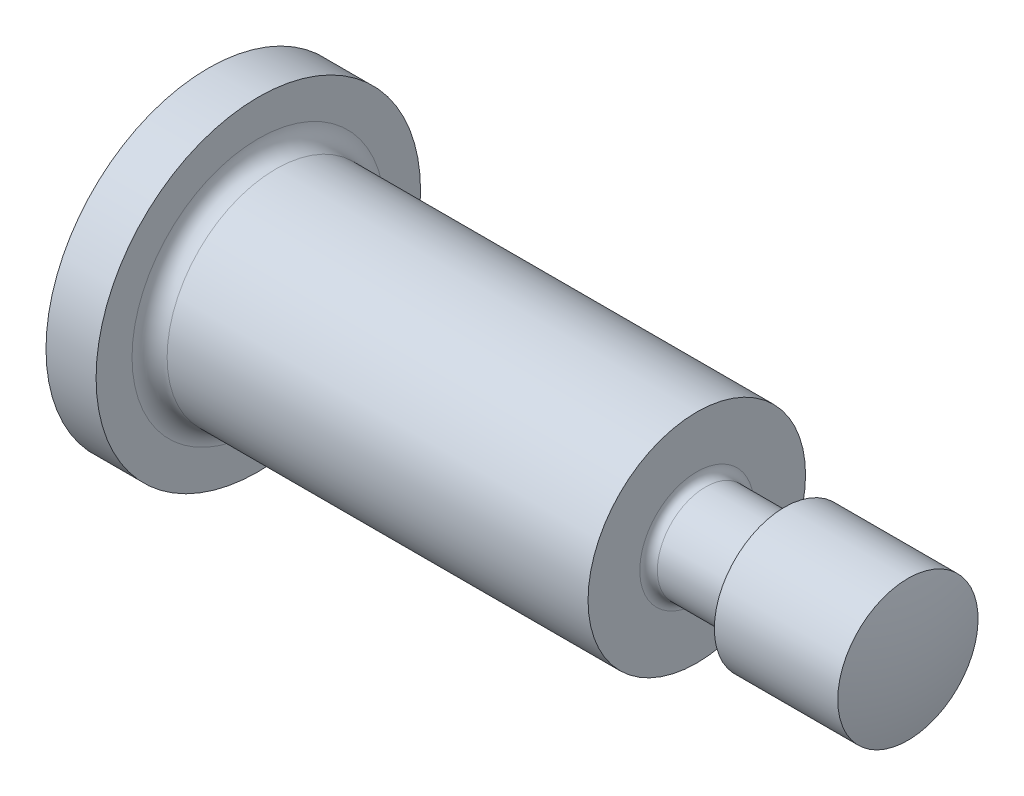
SolidWorks part; units mm, degrees
ref_plane "Front" through (0, 0, 0) normal (0, 0, 1) x (1, 0, 0)
ref_plane "Top" through (0, 0, 0) normal (0, 1, 0) x (1, 0, 0)
ref_plane "Right" through (0, 0, 0) normal (1, 0, 0) x (0, 0, -1)
sketch "Sketch1" plane through (0, 0, 0) normal (1, 0, 0) x (0, 0, -1)
  circle A0 centre (0, 0) radius 1.85
extrude "BaseHead" add sketch "Sketch1" along normal blind 1.1
sketch "Sketch2" plane through (1.1, -0.6091, 0.4548) normal (1, 0, 0) x (0, 0, -1)
  circle A0 centre (0.4548, 0.6091) radius 1.24
  circle A1 centre (0.4548, 0.6091) radius 1.85 construction
  dimension "d1" = 2.48
extrude "BaseBody" add sketch "Sketch2" along normal blind 5
sketch "Sketch3" plane through (6.1, 0.5391, 0.1937) normal (1, 0, 0) x (0, 0, -1)
  circle A0 centre (0.1937, -0.5391) radius 0.8
  circle A2 centre (0.1937, -0.5391) radius 1.24 construction
extrude "BaseEnd" add sketch "Sketch3" along normal blind 2.5
cosmetic thread "ThreadCosmetic1" [suppressed] parameters "THD_MINOR"=1.8
sketch "Sketch4" plane through (-6.1, 0.55, 0) normal (0, 0, 1) x (0, -1, 0)
  line L0 (0.55, 8.528) -> (0.55, -1.878) construction
  line L1 (-5, 13.2) -> (0, 13.2)
  line L2 (-5, 13.2) -> (-5, 12.2)
  line L3 (-5, 12.2) -> (0, 12.2)
  line L4 (0, 13.2) -> (0, 12.2)
  line L7 (1.79, 12.2) -> (-0.69, 12.2) construction
  dimension "D3" = 5
revolve "Cut-Revolve2" cut sketch "Sketch4" angle 360 about L0
fillet "Fillet1" radius 0.1 2 edges at (7.1, 0.55, 0) (6.1, 0.55, 0)
sketch "Sketch5" plane through (-0.85, -0.85, 0) normal (0, 0, 1) x (0, 1, 0)
  line L1 (0.6, -0.85) -> (1.1, -0.85)
  line L2 (0.6, -0.85) -> (0.6, -1.35)
  line L3 (0.6, -1.35) -> (1.1, -1.35)
  line L4 (1.1, -0.85) -> (1.1, -1.35)
  dimension "t" = 0.5
  dimension "m" = 0.25
extrude "Slot" cut sketch "Sketch5" against normal through all and the other way through all
sketch "Sketch6" plane through (-7.5888, 2.0888, 0) normal (0, 0, 1) x (0, -1, 0)
  line L0 (2.0888, 13.2489) -> (2.0888, -3.5713) construction
  line L1 (0.2388, 8.6888) -> (0.2388, 7.5888) construction
  line L3 (2.8888, 16.1888) -> (1.2888, 16.1888) construction
  line L4 (-1.4112, 12.6888) -> (-3.4112, 12.6888)
  line L5 (2.0888, 16.1888) -> (2.0888, 18.1888)
  line L6 (2.0888, 18.1888) -> (-3.4112, 18.1888)
  line L8 (0.2388, 5.5888) -> (2.0888, 5.5888)
  line L9 (2.0888, 5.5888) -> (2.0888, 7.5888)
  line L10 (0.2388, 8.1177) -> (0.2388, 5.5888)
  line L12 (-3.4112, 12.6888) -> (-3.4112, 18.1888)
  arc A0 (0.2388, 8.1177) -> (2.0888, 7.5888) centre (2.0888, 11.0888) ccw
  arc A1 (2.0888, 16.1888) -> (-1.4112, 12.6888) centre (2.0888, 12.6888) ccw
  dimension "D1" = 2
  dimension "r" = 3.5
  dimension "D2" = 2
  dimension "D3" = 2
revolve "BaseTop" cut sketch "Sketch6" angle 360 about L0
fillet "HeadFillet" radius 0.2 1 edges at (1.1, 0, -1.24)
sketch "Sketch7" plane through (0, 0, 0) normal (0, 0, 1) x (1, 0, 0)
  line L0 (8.5073, 0.4969) -> (8.6823, 0.8)
  line L1 (8.6823, 0.8) -> (8.6823, 1.15)
  line L2 (8.6823, 1.15) -> (8.3323, 1.15)
  line L3 (8.3323, 1.15) -> (8.3323, 0.8)
  line L4 (8.3323, 0.8) -> (8.5073, 0.4969)
  line L5 (8.5073, 0.8) -> (8.5073, -0.8) construction
  line L7 (0, 0) -> (9.5069, 0) construction
  dimension "D1" = 0.35
  dimension "D2" = 1.6
revolve "Cut-Revolve10" [suppressed] cut sketch "Sketch7" angle 360 about L7
pattern_linear "LPattern10" [suppressed] count 4 spacing 0.42 along (-1, 0, 0) of bodies 107
equation "\"m@Sketch5\" = \"n@Sketch5\" / 2"
equation "\"D2@Sketch7\" =\"d@Sketch3\""
equation "\"D1@Sketch7\" = ( \"b@BaseEnd\" -\"THD_MINOR@ThreadCosmetic1\")  / 2"
equation "\"D3@LPattern10\" = \"D1@Sketch7\" * 1.2"
equation "\"D1@LPattern10\" = ( \"b@BaseEnd\"  - \"a@Sketch4\" ) / \"D3@LPattern10\" "
